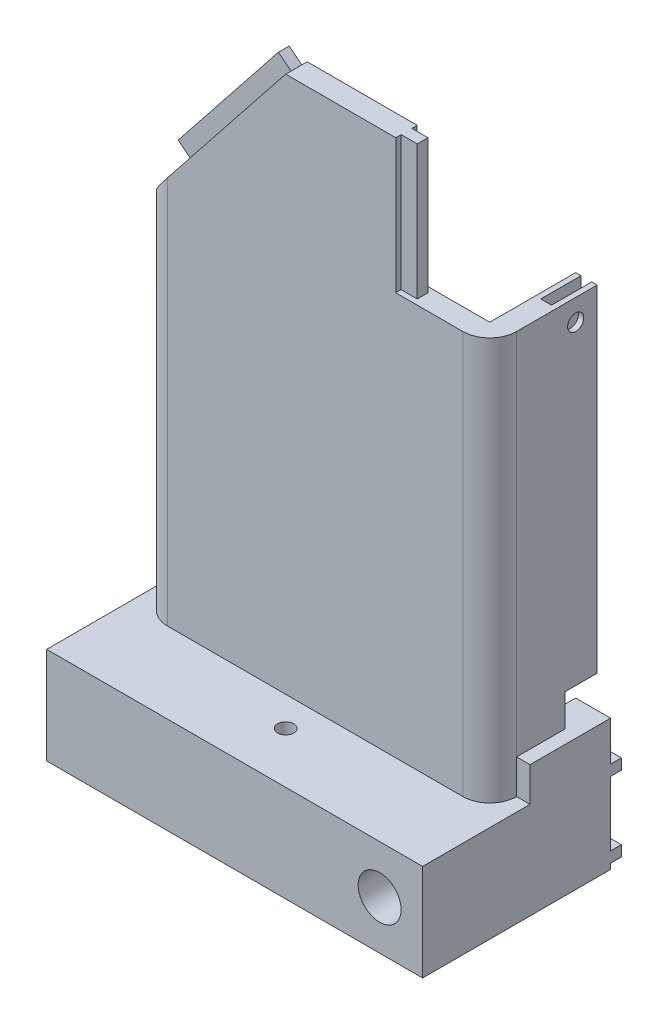
SolidWorks part; units mm, degrees
ref_plane "Front Plane" through (0, 0, 0) normal (0, 0, 1) x (1, 0, 0)
ref_plane "Top Plane" through (0, 0, 0) normal (0, 1, 0) x (1, 0, 0)
ref_plane "Right Plane" through (0, 0, 0) normal (1, 0, 0) x (0, 0, -1)
sketch "Sketch1" plane through (0, 0, 0) normal (0, 1, 0) x (1, 0, 0)
  line L1 (-32.5, -20) -> (32.5, -20)
  line L2 (-32.5, -20) -> (-32.5, 20)
  line L3 (-32.5, 20) -> (32.5, 20)
  line L4 (32.5, -20) -> (32.5, 20)
  line L5 (-32.5, -20) -> (32.5, 20) construction
  line L6 (-32.5, 20) -> (32.5, -20) construction
  point P0 (0, 0)
  dimension "D1" = 65
  dimension "D2" = 40
extrude "Boss-Extrude1" add sketch "Sketch1" along normal blind 100
shell "Shell1" thickness 4 removed face at (0, 0, 0) removed face at (0, 100, 0)
fillet "Fillet1" radius 5 4 edges at (32.5, 50, -20) (32.5, 50, 20) (-32.5, 50, -20) (-32.5, 50, 20)
sketch "Sketch2" plane through (0, 0, 0) normal (0, 0, 1) x (1, 0, 0)
  line L0 (-5.5, 100) -> (-32.5, 66)
  line L1 (28.5, 100) -> (-28.5, 100) construction
  line L2 (-32.5, 100) -> (-32.5, 0) construction
  line L3 (-32.5, 66) -> (-32.5, 100)
  line L4 (-32.5, 100) -> (-5.5, 100)
  dimension "D1" = 5.5
  dimension "D2" = 66
extrude "Cut-Extrude1" cut sketch "Sketch2" against normal through all both and the other way through all
sketch "Sketch3" plane through (0, 0, 0) normal (0, 0, 1) x (1, 0, 0)
  line L1 (32.5, 100) -> (15, 100)
  line L2 (32.5, 100) -> (32.5, 75)
  line L3 (32.5, 75) -> (15, 75)
  line L4 (15, 100) -> (15, 75)
  dimension "D1" = 25
  dimension "D2" = 17.5
extrude "Cut-Extrude2" cut sketch "Sketch3" against normal through all both and the other way through all
sketch "Sketch5" plane through (15, 0, 0) normal (1, 0, 0) x (0, 0, -1)
  line L0 (-18, 100) -> (-18, 75) construction
  line L1 (-16, 100) -> (-20, 100) construction
  line L2 (-16, 75) -> (-20, 75) construction
  line L4 (-19, 100) -> (-17, 100)
  line L5 (-19, 100) -> (-19, 75)
  line L6 (-19, 75) -> (-17, 75)
  line L7 (-17, 100) -> (-17, 75)
  dimension "D1" = 2
extrude "Boss-Extrude2" add sketch "Sketch5" along normal blind 3
mirror "Mirror1" about plane through (0, 0, 0) normal (0, 0, 1) of "Boss-Extrude2"
sketch "Sketch6" plane through (-52.0732, 41.3523, 0) normal (-0.7831, 0.6219, 0) x (0, 0, 1)
  line L0 (-18, 74.8907) -> (-18, 44.8907) construction
  line L1 (-20, 74.8907) -> (-16, 74.8907) construction
  line L3 (-19, 74.8907) -> (-17, 74.8907)
  line L4 (-19, 74.8907) -> (-19, 44.8907)
  line L5 (-19, 44.8907) -> (-17, 44.8907)
  line L6 (-17, 74.8907) -> (-17, 44.8907)
  dimension "D1" = 30
  dimension "D2" = 2
extrude "Boss-Extrude3" add sketch "Sketch6" along normal blind 3
mirror "Mirror2" about plane through (0, 0, 0) normal (0, 0, 1) of "Boss-Extrude3"
sketch "Sketch8" plane through (0, 0, 0) normal (0, 1, 0) x (1, 0, 0)
  line L1 (-35, -35) -> (35, -35)
  line L2 (-35, -35) -> (-35, 35)
  line L3 (-35, 35) -> (35, 35)
  line L4 (35, -35) -> (35, 35)
  line L5 (-35, -35) -> (35, 35) construction
  line L6 (-35, 35) -> (35, -35) construction
  point P0 (0, 0)
  dimension "D1" = 70
  dimension "D2" = 70
extrude "Boss-Extrude4" add sketch "Sketch8" against normal blind 18
sketch "Sketch10" plane through (-35, 0, 0) normal (-1, 0, 0) x (0, 0, 1)
  line L0 (-35, -9) -> (35, -9) construction
  line L1 (-30, -14) -> (30, -14)
  line L2 (-30, -14) -> (-30, -4)
  line L3 (-30, -4) -> (30, -4)
  line L4 (30, -14) -> (30, -4)
  line L5 (-30, -14) -> (30, -4) construction
  line L6 (-30, -4) -> (30, -14) construction
  line L7 (-35, -18) -> (-35, 0) construction
  line L8 (35, -18) -> (35, 0) construction
  line L9 (0, 0) -> (0, -18) construction
  line L10 (-35, -18) -> (35, -18) construction
  point P0 (0, -9)
  dimension "D1" = 60
  dimension "D2" = 10
extrude "Cut-Extrude4" cut sketch "Sketch10" against normal blind 45
sketch "Sketch23" plane through (0, 75, 0) normal (0, 1, 0) x (1, 0, 0)
  line L0 (0, 0) -> (32.5, 0) construction
  line L1 (29.5, 7.5) -> (31.5, 7.5)
  line L2 (29.5, 7.5) -> (29.5, -7.5)
  line L3 (29.5, -7.5) -> (31.5, -7.5)
  line L4 (31.5, 7.5) -> (31.5, -7.5)
  line L5 (32.5, 15) -> (32.5, -15) construction
  line L6 (28.5, 16) -> (28.5, -16) construction
  line L8 (30.5, 14.75) -> (30.5, -14.75) construction
  dimension "D1" = 2
  dimension "D2" = 15
extrude "Cut-Extrude10" cut sketch "Sketch23" against normal blind 10
sketch "Sketch24" plane through (32.5, 0, 0) normal (1, 0, 0) x (0, 0, -1)
  line L1 (15, 75) -> (-15, 75) construction
  circle A0 centre (-4, 71) radius 1.5
  point P2 (0, 75)
  dimension "D3" = 3
  dimension "D1" = 4
  dimension "D2" = 4
extrude "Cut-Extrude11" cut sketch "Sketch24" against normal blind 10 and the other way through all
mirror "Mirror4" about plane through (0, 0, 0) normal (0, 0, 1) of "Cut-Extrude11"
sketch "Sketch27" plane through (0, 0, 0) normal (0, 1, 0) x (1, 0, 0)
  line L0 (35, -35) -> (35, 35) construction
  line L1 (-35, 35) -> (35, 35)
  line L2 (-35, 35) -> (-35, 0)
  line L3 (-35, 0) -> (35, 0)
  line L4 (35, 35) -> (35, 0)
extrude "Cut-Extrude12" cut sketch "Sketch27" against normal through all both and the other way through all
sketch "Sketch29" plane through (0, 0, 0) normal (0, 0, -1) x (-1, 0, 0)
  line L0 (35, -2) -> (-35, -2) construction
  line L1 (35, -4) -> (35, 0) construction
  line L2 (-35, -18) -> (-35, 0) construction
  line L3 (35, -1) -> (-35, -1)
  line L4 (35, -1) -> (35, -3)
  line L5 (35, -3) -> (-35, -3)
  line L6 (-35, -1) -> (-35, -3)
  dimension "D1" = 2
extrude "Boss-Extrude6" add sketch "Sketch29" along normal blind 2
sketch "Sketch30" plane through (0, 0, 0) normal (0, 0, -1) x (-1, 0, 0)
  line L0 (35, -16) -> (-35, -16) construction
  line L1 (35, -18) -> (35, -14) construction
  line L2 (-35, -18) -> (-35, -3) construction
  line L4 (-35, -15) -> (35, -15)
  line L5 (-35, -15) -> (-35, -17)
  line L6 (-35, -17) -> (35, -17)
  line L7 (35, -15) -> (35, -17)
  dimension "D1" = 2
extrude "Boss-Extrude7" add sketch "Sketch30" along normal blind 2
sketch "Sketch31" plane through (0, 0, 35) normal (0, 0, 1) x (1, 0, 0)
  line L0 (35, -18) -> (35, 0) construction
  line L1 (-35, -18) -> (35, -18) construction
  circle A0 centre (27, -9) radius 2
  dimension "D1" = 4
  dimension "D2" = 8
  dimension "D3" = 9
extrude "Cut-Extrude13" cut sketch "Sketch31" against normal through all both and the other way through all
sketch "Sketch32" plane through (0, 0, 35) normal (0, 0, 1) x (1, 0, 0)
  circle A0 centre (27, -9) radius 4
  dimension "D1" = 8
extrude "Cut-Extrude14" cut sketch "Sketch32" against normal blind 15
sketch "Sketch34" plane through (0, 0, 0) normal (0, 1, 0) x (1, 0, 0)
  line L0 (-35, 2) -> (35, 2) construction
  line L1 (-35, 0) -> (-35, -35) construction
  circle A0 centre (0, -25.5) radius 1.5
  dimension "D1" = 3
  dimension "D2" = 27.5
  dimension "D3" = 35
extrude "Cut-Extrude15" cut sketch "Sketch34" against normal through all both and the other way through all
sketch "Sketch35" plane through (0, 0, 0) normal (0, 1, 0) x (1, 0, 0)
  line L1 (-35, 0) -> (35, 0) construction
  line L2 (28.5, -16) -> (28.5, 0) construction
  circle A0 centre (21, -10.5) radius 3
  dimension "D1" = 6
  dimension "D2" = 10.5
  dimension "D3" = 7.5
extrude "Boss-Extrude8" add sketch "Sketch35" along normal blind 7
sketch "Sketch36" plane through (0, 7, 0) normal (0, 1, 0) x (1, 0, 0)
  circle A0 centre (21, -10.5) radius 1.75
  dimension "D1" = 3.5
extrude "Cut-Extrude16" cut sketch "Sketch36" against normal blind 4
pattern_linear "LPattern1" count 2 spacing 43.5 along (-1, 0, 0) of "Boss-Extrude8", "Cut-Extrude16"
sketch "Sketch37" plane through (32.5, 0, 0) normal (1, 0, 0) x (0, 0, -1)
  line L0 (0, 0) -> (0, 75) construction
  line L1 (0, 12.4) -> (-6, 12.4)
  line L2 (0, 12.4) -> (0, 6.4)
  line L3 (0, 6.4) -> (-6, 6.4)
  line L4 (-6, 12.4) -> (-6, 6.4)
  line L5 (-15, 0) -> (0, 0) construction
  dimension "D1" = 6
  dimension "D2" = 6
  dimension "D3" = 6.4
extrude "Cut-Extrude17" cut sketch "Sketch37" against normal through all both and the other way through all
sketch "Sketch38" plane through (32.5, 0, 0) normal (1, 0, 0) x (0, 0, -1)
  line L1 (0, 6.4) -> (-15, 6.4)
  line L2 (0, 6.4) -> (0, 0)
  line L3 (0, 0) -> (-15, 0)
  line L4 (-15, 6.4) -> (-15, 0)
extrude "Boss-Extrude9" add sketch "Sketch38" along normal up to surface (2.5 mm away) up to face at (35, -9, 5.1667)
sketch "Sketch41" plane through (0, -18, 0) normal (0, -1, 0) x (-1, 0, 0)
  circle A0 centre (0, -25.5) radius 4
  dimension "D1" = 8
extrude "Cut-Extrude18" cut sketch "Sketch41" against normal blind 3
